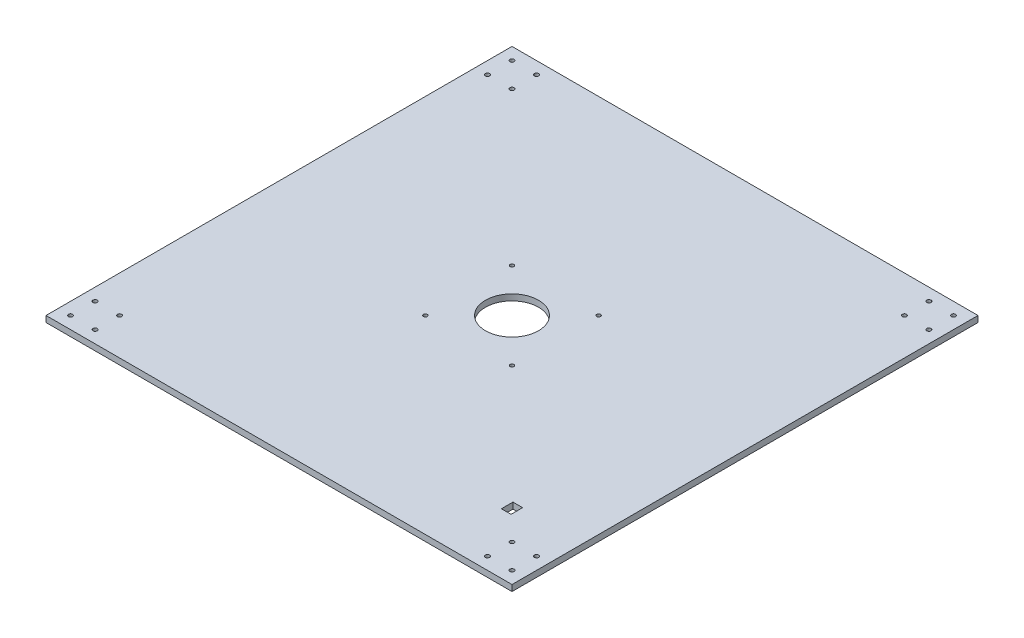
SolidWorks part; units mm, degrees
ref_plane "Front Plane" through (0, 0, 0) normal (0, 0, 1) x (1, 0, 0)
ref_plane "Top Plane" through (0, 0, 0) normal (0, 1, 0) x (1, 0, 0)
ref_plane "Right Plane" through (0, 0, 0) normal (1, 0, 0) x (0, 0, -1)
sketch "Sketch1" plane through (0, 0, 0) normal (0, 1, 0) x (1, 0, 0)
  line L1 (-241.3, -241.3) -> (241.3, -241.3)
  line L2 (-241.3, -241.3) -> (-241.3, 241.3)
  line L3 (-241.3, 241.3) -> (241.3, 241.3)
  line L4 (241.3, -241.3) -> (241.3, 241.3)
  line L5 (-241.3, -241.3) -> (241.3, 241.3) construction
  line L6 (-241.3, 241.3) -> (241.3, -241.3) construction
  point P0 (0, 0)
  dimension "D1" = 482.6
  dimension "D2" = 482.6
extrude "Boss-Extrude1" add sketch "Sketch1" along normal blind 6.35
sketch "Sketch2" plane through (0, 6.35, 0) normal (0, 1, 0) x (1, 0, 0)
  line L1 (-44.8437, -44.8437) -> (44.8437, -44.8437) construction
  line L2 (-44.8437, -44.8437) -> (-44.8437, 44.8437) construction
  line L3 (-44.8437, 44.8437) -> (44.8437, 44.8437) construction
  line L4 (44.8437, -44.8437) -> (44.8437, 44.8437) construction
  line L5 (-44.8437, -44.8437) -> (44.8437, 44.8437) construction
  line L6 (-44.8437, 44.8437) -> (44.8437, -44.8437) construction
  circle A0 centre (-44.8437, 44.8437) radius 1.9844
  circle A1 centre (44.8437, 44.8437) radius 1.9844
  circle A2 centre (-44.8437, -44.8437) radius 1.9844
  circle A3 centre (44.8437, -44.8437) radius 1.9844
  circle A4 centre (0, 0) radius 27.432
  point P0 (0, 0)
  dimension "D3" = 3.9688
  dimension "D4" = 54.864
  dimension "D1" = 89.6874
  dimension "D2" = 89.6874
extrude "Cut-Extrude1" cut sketch "Sketch2" against normal through all and the other way through all
sketch "Sketch3" plane through (0, 6.35, 0) normal (0, 1, 0) x (1, 0, 0)
  line L1 (0, 0) -> (241.3, -241.3) construction
  line L8 (167.8699, -178.8699) -> (177.8699, -178.8699)
  line L9 (167.8699, -178.8699) -> (167.8699, -166.8699)
  line L10 (167.8699, -166.8699) -> (177.8699, -166.8699)
  line L11 (177.8699, -178.8699) -> (177.8699, -166.8699)
  line L12 (167.8699, -178.8699) -> (177.8699, -166.8699) construction
  line L13 (167.8699, -166.8699) -> (177.8699, -178.8699) construction
  point P9 (172.8699, -172.8699)
  dimension "D1" = 244.475
  dimension "D4" = 12
extrude "Cut-Extrude2" cut sketch "Sketch3" against normal through all
sketch "Sketch4" plane through (0, 6.35, 0) normal (0, 1, 0) x (1, 0, 0)
  line L0 (241.3, 241.3) -> (-241.3, 241.3) construction
  line L1 (-215.9, 215.9) -> (215.9, 215.9) construction
  line L2 (-215.9, 215.9) -> (-215.9, -215.9) construction
  line L3 (-215.9, -215.9) -> (215.9, -215.9) construction
  line L4 (215.9, 215.9) -> (215.9, -215.9) construction
  line L5 (-215.9, 215.9) -> (215.9, -215.9) construction
  line L6 (-215.9, -215.9) -> (215.9, 215.9) construction
  line L7 (-241.3, 241.3) -> (-241.3, -241.3) construction
  line L9 (-228.6, 228.6) -> (-203.2, 228.6) construction
  line L10 (-228.6, 228.6) -> (-228.6, 203.2) construction
  line L11 (-228.6, 203.2) -> (-203.2, 203.2) construction
  line L12 (-203.2, 228.6) -> (-203.2, 203.2) construction
  line L13 (-228.6, 228.6) -> (-203.2, 203.2) construction
  line L14 (-228.6, 203.2) -> (-203.2, 228.6) construction
  line L15 (-228.6, -228.6) -> (-203.2, -228.6) construction
  line L16 (-228.6, -228.6) -> (-228.6, -203.2) construction
  line L17 (-228.6, -203.2) -> (-203.2, -203.2) construction
  line L18 (-203.2, -228.6) -> (-203.2, -203.2) construction
  line L19 (-228.6, -228.6) -> (-203.2, -203.2) construction
  line L20 (-228.6, -203.2) -> (-203.2, -228.6) construction
  line L21 (228.6, -228.6) -> (203.2, -228.6) construction
  line L22 (228.6, -228.6) -> (228.6, -203.2) construction
  line L23 (228.6, -203.2) -> (203.2, -203.2) construction
  line L24 (203.2, -228.6) -> (203.2, -203.2) construction
  line L25 (228.6, -228.6) -> (203.2, -203.2) construction
  line L26 (228.6, -203.2) -> (203.2, -228.6) construction
  line L27 (228.6, 228.6) -> (203.2, 228.6) construction
  line L28 (228.6, 228.6) -> (228.6, 203.2) construction
  line L29 (228.6, 203.2) -> (203.2, 203.2) construction
  line L30 (203.2, 228.6) -> (203.2, 203.2) construction
  line L31 (228.6, 228.6) -> (203.2, 203.2) construction
  line L32 (228.6, 203.2) -> (203.2, 228.6) construction
  circle A0 centre (-228.6, 228.6) radius 2.1828
  circle A1 centre (-203.2, 228.6) radius 2.1828
  circle A2 centre (-228.6, 203.2) radius 2.1828
  circle A3 centre (-203.2, 203.2) radius 2.1828
  circle A4 centre (203.2, 228.6) radius 2.1828
  circle A5 centre (203.2, 203.2) radius 2.1828
  circle A6 centre (228.6, 203.2) radius 2.1828
  circle A7 centre (228.6, 228.6) radius 2.1828
  circle A8 centre (203.2, -203.2) radius 2.1828
  circle A9 centre (228.6, -203.2) radius 2.1828
  circle A10 centre (228.6, -228.6) radius 2.1828
  circle A11 centre (203.2, -228.6) radius 2.1828
  circle A12 centre (-228.6, -203.2) radius 2.1828
  circle A13 centre (-203.2, -203.2) radius 2.1828
  circle A14 centre (-203.2, -228.6) radius 2.1828
  circle A15 centre (-228.6, -228.6) radius 2.1828
  point P0 (0, 0)
  dimension "D4" = 4.3656
  dimension "D1" = 25.4
  dimension "D2" = 25.4
  dimension "D3" = 25.4
extrude "Cut-Extrude3" cut sketch "Sketch4" against normal through all
